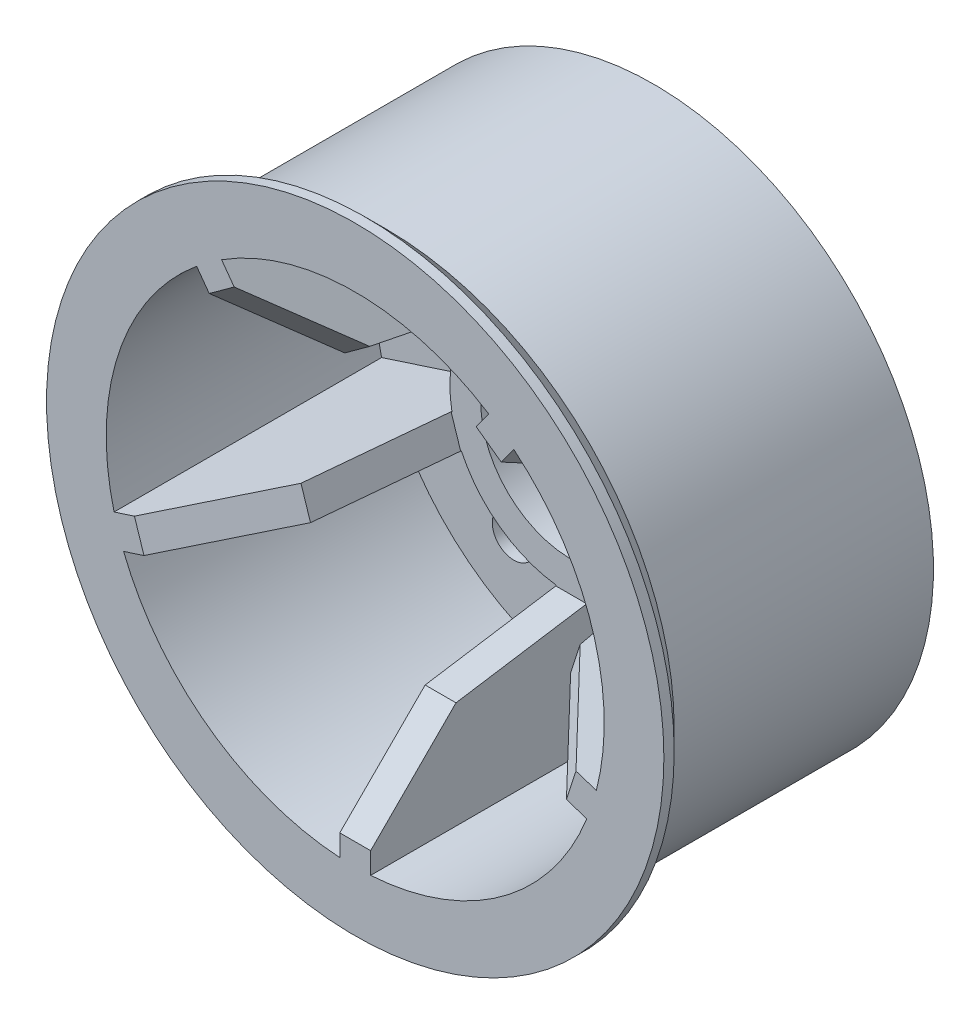
SolidWorks part; units mm, degrees
ref_plane "Спереди" through (0, 0, 0) normal (0, 0, 1) x (1, 0, 0)
ref_plane "Сверху" through (0, 0, 0) normal (0, 1, 0) x (1, 0, 0)
ref_plane "Справа" through (0, 0, 0) normal (1, 0, 0) x (0, 0, -1)
sketch "Эскиз1" [suppressed] plane through (0, 0, 0) normal (0, 0, 1) x (1, 0, 0)
  circle A0 centre (0, 0) radius 30
  dimension "D1" = 60
extrude "Бобышка-Вытянуть1" [suppressed] add sketch "Эскиз1" along normal blind 3
sketch "Эскиз2" [suppressed] plane through (0, 0, 3) normal (0, 0, 1) x (1, 0, 0)
  circle A0 centre (0, 0) radius 27.2
  dimension "D1" = 54.4
extrude "Бобышка-Вытянуть2" [suppressed] add sketch "Эскиз2" along normal blind 10
chamfer "Фаска1" [suppressed] distance 2 angle 45
sketch "Эскиз3" [suppressed] plane through (0, 0, 0) normal (0, 0, -1) x (-1, 0, 0)
  line L0 (-3.5218, 6.1) -> (3.5218, 6.1)
  line L1 (3.5218, 6.1) -> (7.0437, 0)
  line L2 (7.0437, 0) -> (3.5218, -6.1)
  line L3 (3.5218, -6.1) -> (-3.5218, -6.1)
  line L4 (-3.5218, -6.1) -> (-7.0437, 0)
  line L5 (-7.0437, 0) -> (-3.5218, 6.1)
  circle A0 centre (0, 0) radius 6.1 construction
  dimension "D1" = 12.2
extrude "Вырез-Вытянуть1" [suppressed] cut sketch "Эскиз3" against normal blind 7
sketch "Эскиз4" [suppressed] plane through (0, 0, 0) normal (0, 0, -1) x (-1, 0, 0)
  line L0 (0, 0) -> (0, 18) construction
  line L1 (-2.0785, 21.6) -> (2.0785, 21.6)
  line L2 (2.0785, 21.6) -> (4.1569, 18)
  line L3 (4.1569, 18) -> (2.0785, 14.4)
  line L4 (2.0785, 14.4) -> (-2.0785, 14.4)
  line L5 (-2.0785, 14.4) -> (-4.1569, 18)
  line L6 (-4.1569, 18) -> (-2.0785, 21.6)
  circle A0 centre (0, 18) radius 3.6 construction
  dimension "D2" = 7.2
  dimension "D1" = 18
extrude "Вырез-Вытянуть2" [suppressed] cut sketch "Эскиз4" against normal blind 3.5
sketch "Эскиз5" [suppressed] plane through (0, 0, 3.5) normal (0, 0, -1) x (-1, 0, 0)
  line L0 (0, 0) -> (0, 18) construction
  line L1 (2.0785, 14.4) -> (4.1569, 18) construction
  line L2 (2.0785, 21.6) -> (-2.0785, 21.6) construction
  circle A0 centre (0, 18) radius 3.6 construction
  circle A1 centre (0, 18) radius 2.1
  dimension "D1" = 4.2
extrude "Вырез-Вытянуть3" [suppressed] cut sketch "Эскиз5" against normal through all
sketch "Эскиз6" [suppressed] plane through (0, 0, 7) normal (0, 0, -1) x (-1, 0, 0)
  circle A0 centre (0, 0) radius 2.1
  dimension "D1" = 4.2
extrude "Вырез-Вытянуть4" [suppressed] cut sketch "Эскиз6" against normal through all
pattern_circular "Круговой массив1" [suppressed] count 5 over 360 of bodies 108
sketch "Эскиз7" plane through (0, 0, 0) normal (0, 0, 1) x (1, 0, 0)
  circle A0 centre (0, 0) radius 27.2
  dimension "D1" = 54.4
extrude "Бобышка-Вытянуть3" add sketch "Эскиз7" along normal blind 26
sketch "Эскиз8" plane through (0, 0, 26) normal (0, 0, 1) x (1, 0, 0)
  circle A0 centre (0, 0) radius 30
  dimension "D1" = 60
extrude "Бобышка-Вытянуть4" add sketch "Эскиз8" along normal blind 3
sketch "Эскиз9" plane through (0, 0, 29) normal (0, 0, 1) x (1, 0, 0)
  circle A0 centre (0, 0) radius 24.2
  dimension "D1" = 48.4
extrude "Вырез-Вытянуть5" cut sketch "Эскиз9" against normal blind 26
sketch "Эскиз10" plane through (0, 0, 0) normal (0, 0, -1) x (-1, 0, 0)
  line L0 (0, 0) -> (0, 18) construction
  circle A0 centre (0, 0) radius 2.1
  circle A1 centre (0, 18) radius 2.1
  dimension "D2" = 4.2
  dimension "D3" = 4.2
  dimension "D1" = 18
extrude "Вырез-Вытянуть6" cut sketch "Эскиз10" against normal through all
pattern_circular "Круговой массив2" count 5 over 360 about axis through (0, 0, 29) along (0, 0, -1) of "Вырез-Вытянуть6"
sketch "Эскиз11" plane through (0, 0, 3) normal (0, 0, 1) x (1, 0, 0)
  line L0 (0, 8.8) -> (0, 11.8) construction
  circle A0 centre (0, 0) radius 11.8
  circle A1 centre (0, 0) radius 8.8
  circle A2 centre (0, 18) radius 6.2 construction
  circle A3 centre (0, 0) radius 24.2 construction
  dimension "D1" = 3
extrude "Бобышка-Вытянуть5" add sketch "Эскиз11" along normal blind 5
sketch "Эскиз13" plane through (0, 0, 0) normal (1, 0, 0) x (0, 0, -1)
  line L0 (-8, -11.7936) -> (-29, -15.0736)
  line L1 (-8, 11.8) -> (-8, -11.8) construction
  line L2 (-29, 24.2) -> (-29, -24.2) construction
  line L3 (-29, -15.0736) -> (-29, -25.0736)
  line L4 (-29, 30) -> (-29, -30) construction
  line L5 (-29, -25.0736) -> (-3, -25.0736)
  line L6 (-3, -25.0736) -> (-3, -10.7936)
  line L7 (-3, 11.8) -> (-3, -11.8) construction
  line L8 (-3, -10.7936) -> (-8, -10.7936)
  line L9 (-8, -10.7936) -> (-8, -11.7936)
  dimension "D1" = 1
  dimension "D2" = 10
extrude "Бобышка-Вытянуть6" add sketch "Эскиз13" along normal blind 1.5 and the other way blind 1.5
chamfer "Фаска2" distance 7 angle 45 1 edges at (0, -15.0736, 29) first distance on face at (0, -7.5252, 29)
pattern_circular "Круговой массив3" count 5 over 360 about axis through (0, 0, 29) along (0, 0, -1) of "Бобышка-Вытянуть6", "Фаска2" reverse direction yes
chamfer "Фаска3" distance 2 angle 45 1 edges at (30, 0, 26)
